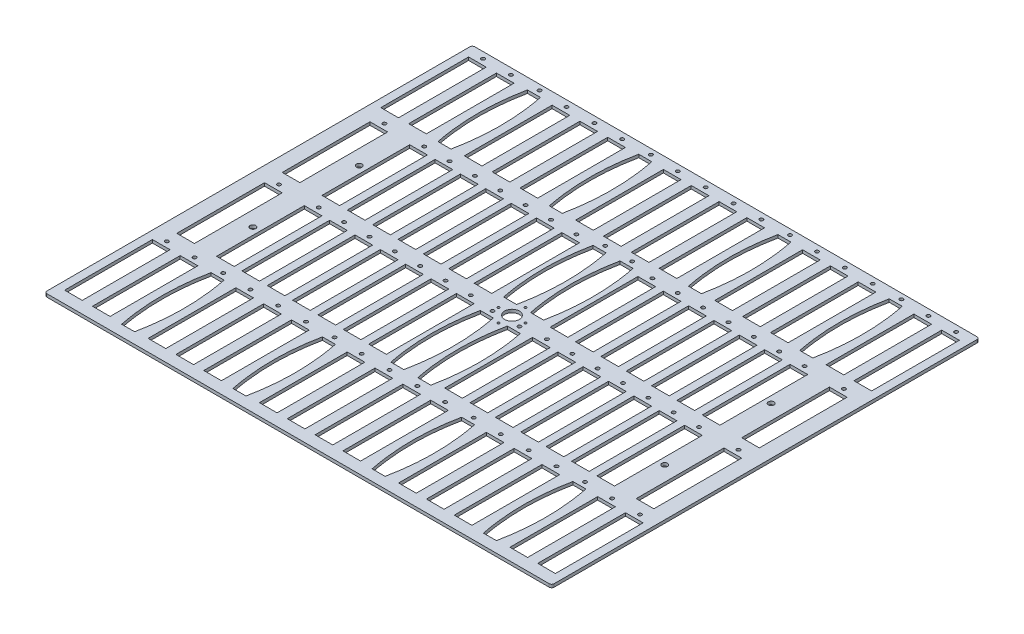
SolidWorks part; units mm, degrees
ref_plane "Front Plane" through (0, 0, 0) normal (0, 0, 1) x (1, 0, 0)
ref_plane "Top Plane" through (0, 0, 0) normal (0, 1, 0) x (1, 0, 0)
ref_plane "Right Plane" through (0, 0, 0) normal (1, 0, 0) x (0, 0, -1)
sketch "Sketch1" plane through (0, 0, 0) normal (0, 1, 0) x (1, 0, 0)
  line L1 (-262.7312, -221.6379) -> (262.7312, -221.6379)
  line L2 (-262.7312, -221.6379) -> (-262.7312, 221.6379)
  line L3 (-262.7312, 221.6379) -> (262.7312, 221.6379)
  line L4 (262.7312, -221.6379) -> (262.7312, 221.6379)
  line L5 (-262.7312, -221.6379) -> (262.7312, 221.6379) construction
  line L6 (-262.7312, 221.6379) -> (262.7312, -221.6379) construction
  point P0 (0, 0)
  dimension "D1" = 525.4625
  dimension "D2" = 443.2757
extrude "Boss-Extrude1" add sketch "Sketch1" along normal blind 3.175
sketch "Sketch2" plane through (0, 3.175, 0) normal (0, 1, 0) x (1, 0, 0)
  circle A0 centre (0, 0) radius 7.62
  dimension "D1" = 15.24
extrude "Cut-Extrude1" cut sketch "Sketch2" against normal through all
hole_wizard "#2 Clearance Hole1" positions "Sketch3" profile "Sketch4" hole size "#2" standard "ANSI Inch" end condition through all
sketch "Sketch3" plane through (0, 3.175, 0) normal (0, 1, 0) x (1, 0, 0)
  line L0 (0, 0) -> (0, 13.97) construction
  line L2 (0, 0) -> (13.97, 0) construction
  line L3 (0, 0) -> (0, -13.97) construction
  line L4 (0, 0) -> (-13.97, 0) construction
  point P194 (0, 13.97)
  point P202 (13.97, 0)
  point P203 (0, -13.97)
  point P204 (-13.97, 0)
  point P205 (0, 0)
  dimension "D1" = 4
  dimension "D2" = 13.97
sketch "Sketch4" plane through (0, 3.175, 0) normal (1, 0, 0) x (0, 0, 1)
  line L0 (0, 0) -> (0, 3.175)
  line L1 (0, 3.175) -> (1.2192, 3.175)
  line L2 (1.2192, 3.175) -> (1.2192, 0)
  line L5 (1.2192, 0) -> (0, 0)
  line L11 (0, -6.35) -> (0, 107.95) construction
  dimension "Thru Hole Dia." = 2.4384
  dimension "Thru Hole Depth" = 3.175
hole_wizard "#1 (0.228) Diameter Hole1" positions "Sketch6" profile "Sketch7" hole size "#1" standard "ANSI Inch" end condition through all
sketch "Sketch6" plane through (0, 3.175, 0) normal (0, 1, 0) x (1, 0, 0)
  line L1 (-213.36, -55.1011) -> (213.36, -55.1011) construction
  line L2 (-213.36, -55.1011) -> (-213.36, 55.1011) construction
  line L3 (-213.36, 55.1011) -> (213.36, 55.1011) construction
  line L4 (213.36, -55.1011) -> (213.36, 55.1011) construction
  line L5 (-213.36, -55.1011) -> (213.36, 55.1011) construction
  line L6 (-213.36, 55.1011) -> (213.36, -55.1011) construction
  circle A0 centre (0, 0) radius 7.62 construction
  point P2 (213.36, 55.1011)
  point P11 (-213.36, -55.1011)
  point P12 (-213.36, 55.1011)
  point P13 (213.36, -55.1011)
  point P26 (-213.36, 55.1011)
  point P28 (213.36, 55.1011)
  point P30 (213.36, -55.1011)
  point P32 (-213.36, -55.1011)
  dimension "D1" = 426.72
  dimension "D2" = 110.2021
  dimension "D3" = 213.36
  dimension "D4" = 55.1011
sketch "Sketch7" plane through (213.36, 3.175, -55.1011) normal (1, 0, 0) x (0, 0, 1)
  line L0 (0, 0) -> (0, 3.175)
  line L1 (0, 3.175) -> (2.8956, 3.175)
  line L2 (2.8956, 3.175) -> (2.8956, 0)
  line L5 (2.8956, 0) -> (0, 0)
  line L11 (0, -6.35) -> (0, 107.95) construction
  dimension "Thru Hole Dia." = 5.7912
  dimension "Thru Hole Depth" = 3.175
sketch "Sketch5" plane through (0, 3.175, 0) normal (0, 1, 0) x (1, 0, 0)
  line L0 (-262.7312, 163.8275) -> (262.7312, 163.8275) construction
  line L1 (-198.8875, 163.8275) -> (-176.0275, 163.8275) construction
  line L2 (-245.1367, 221.6379) -> (-245.1367, -221.6379) construction
  line L3 (-262.7312, 221.6379) -> (-262.7312, -221.6379) construction
  line L4 (-262.7312, -221.6379) -> (262.7312, -221.6379) construction
  line L5 (-216.2971, 221.6379) -> (-216.2971, -221.6379) construction
  line L6 (262.7312, -221.6379) -> (262.7312, 221.6379) construction
  line L7 (-187.4575, 221.6379) -> (-187.4575, -221.6379) construction
  line L8 (-262.7312, 54.6066) -> (262.7312, 54.6066) construction
  line L9 (-262.7312, -54.6142) -> (262.7312, -54.6142) construction
  line L10 (-262.7312, -163.8351) -> (262.7312, -163.8351) construction
  line L11 (262.7312, 221.6379) -> (-262.7312, 221.6379) construction
  line L12 (-158.6179, 221.6379) -> (-158.6179, -221.6379) construction
  line L13 (-129.7783, 221.6379) -> (-129.7783, -221.6379) construction
  line L14 (-100.9388, 221.6379) -> (-100.9388, -221.6379) construction
  line L15 (-72.0992, 221.6379) -> (-72.0992, -221.6379) construction
  line L16 (-43.2596, 221.6379) -> (-43.2596, -221.6379) construction
  line L17 (-14.42, 221.6379) -> (-14.42, -221.6379) construction
  line L18 (14.4196, 221.6379) -> (14.4196, -221.6379) construction
  line L19 (43.2592, 221.6379) -> (43.2592, -221.6379) construction
  line L20 (72.0987, 221.6379) -> (72.0987, -221.6379) construction
  line L21 (100.9383, 221.6379) -> (100.9383, -221.6379) construction
  line L22 (129.7779, 221.6379) -> (129.7779, -221.6379) construction
  line L23 (158.6175, 221.6379) -> (158.6175, -221.6379) construction
  line L24 (187.4571, 221.6379) -> (187.4571, -221.6379) construction
  line L25 (216.2967, 221.6379) -> (216.2967, -221.6379) construction
  line L26 (245.1362, 221.6379) -> (245.1362, -221.6379) construction
  line L27 (-225.4415, 209.2935) -> (-207.1535, 209.2935)
  line L28 (-254.2807, 209.2935) -> (-235.9927, 209.2935)
  line L29 (-254.2807, 209.2935) -> (-254.2807, 118.3615)
  line L30 (-254.2807, 118.3615) -> (-235.9927, 118.3615)
  line L31 (-235.9927, 209.2935) -> (-235.9927, 118.3615)
  line L32 (-254.2807, 209.2935) -> (-235.9927, 118.3615) construction
  line L33 (-254.2807, 118.3615) -> (-235.9927, 209.2935) construction
  line L34 (-254.2807, -118.3691) -> (-235.9927, -118.3691)
  line L35 (-254.2807, -118.3691) -> (-254.2807, -209.3011)
  line L36 (-254.2807, -209.3011) -> (-235.9927, -209.3011)
  line L37 (-235.9927, -118.3691) -> (-235.9927, -209.3011)
  line L38 (-254.2807, -118.3691) -> (-235.9927, -209.3011) construction
  line L39 (-254.2807, -209.3011) -> (-235.9927, -118.3691) construction
  line L40 (-225.4415, 209.2935) -> (-225.4415, 118.3615)
  line L41 (-207.1535, 209.2935) -> (-207.1535, 118.3615)
  line L42 (-225.4415, 118.3615) -> (-207.1535, 118.3615)
  line L43 (-225.4415, -118.3691) -> (-207.1535, -118.3691)
  line L44 (-207.1535, -118.3691) -> (-207.1535, -209.3011)
  line L45 (-225.4415, -118.3691) -> (-225.4415, -209.3011)
  line L46 (-225.4415, -209.3011) -> (-207.1535, -209.3011)
  line L47 (-194.1885, 210.1825) -> (-180.7265, 210.1825)
  line L48 (-194.1885, 210.1825) -> (-194.1885, 117.4725) construction
  line L49 (-194.1885, 117.4725) -> (-180.7265, 117.4725)
  line L50 (-180.7265, 210.1825) -> (-180.7265, 117.4725) construction
  line L51 (-194.1885, 210.1825) -> (-180.7265, 117.4725) construction
  line L52 (-194.1885, 117.4725) -> (-180.7265, 210.1825) construction
  line L53 (-78.8302, 210.1825) -> (-65.3682, 210.1825)
  line L54 (-78.8302, 117.4725) -> (-65.3682, 117.4725)
  line L55 (-167.7632, 209.2935) -> (-149.4752, 209.2935)
  line L56 (-167.7632, 209.2935) -> (-167.7632, 118.3615)
  line L57 (-149.4752, 209.2935) -> (-149.4752, 118.3615)
  line L58 (-167.7632, 118.3615) -> (-149.4752, 118.3615)
  line L59 (-167.7632, -118.3691) -> (-149.4752, -118.3691)
  line L60 (-149.4752, -118.3691) -> (-149.4752, -209.3011)
  line L61 (-167.7632, -118.3691) -> (-167.7632, -209.3011)
  line L62 (-167.7632, -209.3011) -> (-149.4752, -209.3011)
  line L63 (-138.924, 209.2935) -> (-120.636, 209.2935)
  line L64 (-138.924, 209.2935) -> (-138.924, 118.3615)
  line L65 (-120.636, 209.2935) -> (-120.636, 118.3615)
  line L66 (-138.924, 118.3615) -> (-120.636, 118.3615)
  line L67 (-138.924, -118.3691) -> (-120.636, -118.3691)
  line L68 (-120.636, -118.3691) -> (-120.636, -209.3011)
  line L69 (-138.924, -118.3691) -> (-138.924, -209.3011)
  line L70 (-138.924, -209.3011) -> (-120.636, -209.3011)
  line L71 (-110.0849, 209.2935) -> (-91.7969, 209.2935)
  line L72 (-110.0849, 209.2935) -> (-110.0849, 118.3615)
  line L73 (-91.7969, 209.2935) -> (-91.7969, 118.3615)
  line L74 (-110.0849, 118.3615) -> (-91.7969, 118.3615)
  line L75 (-110.0849, -118.3691) -> (-91.7969, -118.3691)
  line L76 (-91.7969, -118.3691) -> (-91.7969, -209.3011)
  line L77 (-110.0849, -118.3691) -> (-110.0849, -209.3011)
  line L78 (-110.0849, -209.3011) -> (-91.7969, -209.3011)
  line L79 (65.3677, 210.1825) -> (78.8297, 210.1825)
  line L80 (65.3677, 117.4725) -> (78.8297, 117.4725)
  line L81 (180.7261, 210.1825) -> (194.1881, 210.1825)
  line L82 (180.7261, 117.4725) -> (194.1881, 117.4725)
  line L83 (-194.1885, -117.6299) -> (-180.7265, -117.6299)
  line L84 (-194.1885, -210.3399) -> (-180.7265, -210.3399)
  line L85 (-78.8302, -117.6299) -> (-65.3682, -117.6299)
  line L86 (-78.8302, -210.3399) -> (-65.3682, -210.3399)
  line L87 (-52.4065, 209.2935) -> (-34.1185, 209.2935)
  line L88 (-52.4065, 209.2935) -> (-52.4065, 118.3615)
  line L89 (-34.1185, 209.2935) -> (-34.1185, 118.3615)
  line L90 (-52.4065, 118.3615) -> (-34.1185, 118.3615)
  line L91 (-52.4065, -118.3691) -> (-34.1185, -118.3691)
  line L92 (-34.1185, -118.3691) -> (-34.1185, -209.3011)
  line L93 (-52.4065, -118.3691) -> (-52.4065, -209.3011)
  line L94 (-52.4065, -209.3011) -> (-34.1185, -209.3011)
  line L95 (-23.5674, 209.2935) -> (-5.2794, 209.2935)
  line L96 (-23.5674, 209.2935) -> (-23.5674, 118.3615)
  line L97 (-5.2794, 209.2935) -> (-5.2794, 118.3615)
  line L98 (-23.5674, 118.3615) -> (-5.2794, 118.3615)
  line L99 (-23.5674, -118.3691) -> (-5.2794, -118.3691)
  line L100 (-5.2794, -118.3691) -> (-5.2794, -209.3011)
  line L101 (-23.5674, -118.3691) -> (-23.5674, -209.3011)
  line L102 (-23.5674, -209.3011) -> (-5.2794, -209.3011)
  line L103 (5.2718, 209.2935) -> (23.5598, 209.2935)
  line L104 (5.2718, 209.2935) -> (5.2718, 118.3615)
  line L105 (23.5598, 209.2935) -> (23.5598, 118.3615)
  line L106 (5.2718, 118.3615) -> (23.5598, 118.3615)
  line L107 (5.2718, -118.3691) -> (23.5598, -118.3691)
  line L108 (23.5598, -118.3691) -> (23.5598, -209.3011)
  line L109 (5.2718, -118.3691) -> (5.2718, -209.3011)
  line L110 (5.2718, -209.3011) -> (23.5598, -209.3011)
  line L111 (34.1109, 209.2935) -> (52.3989, 209.2935)
  line L112 (34.1109, 209.2935) -> (34.1109, 118.3615)
  line L113 (52.3989, 209.2935) -> (52.3989, 118.3615)
  line L114 (34.1109, 118.3615) -> (52.3989, 118.3615)
  line L115 (34.1109, -118.3691) -> (52.3989, -118.3691)
  line L116 (52.3989, -118.3691) -> (52.3989, -209.3011)
  line L117 (34.1109, -118.3691) -> (34.1109, -209.3011)
  line L118 (34.1109, -209.3011) -> (52.3989, -209.3011)
  line L119 (180.7261, -117.6299) -> (194.1881, -117.6299)
  line L120 (180.7261, -210.3399) -> (194.1881, -210.3399)
  line L121 (65.3677, -210.3399) -> (78.8297, -210.3399)
  line L122 (65.3677, -117.6299) -> (78.8297, -117.6299)
  line L127 (91.7892, 209.2935) -> (110.0772, 209.2935)
  line L128 (91.7892, 209.2935) -> (91.7893, 118.3615)
  line L129 (110.0772, 209.2935) -> (110.0773, 118.3615)
  line L130 (91.7893, 118.3615) -> (110.0773, 118.3615)
  line L131 (91.7893, -118.3691) -> (110.0773, -118.3691)
  line L132 (110.0773, -118.3691) -> (110.0773, -209.3011)
  line L133 (91.7893, -118.3691) -> (91.7893, -209.3011)
  line L134 (91.7893, -209.3011) -> (110.0773, -209.3011)
  line L135 (120.6284, 209.2935) -> (138.9164, 209.2935)
  line L136 (120.6284, 209.2935) -> (120.6284, 118.3615)
  line L137 (138.9164, 209.2935) -> (138.9164, 118.3615)
  line L138 (120.6284, 118.3615) -> (138.9164, 118.3615)
  line L139 (120.6284, -118.3691) -> (138.9164, -118.3691)
  line L140 (138.9164, -118.3691) -> (138.9164, -209.3011)
  line L141 (120.6284, -118.3691) -> (120.6284, -209.3011)
  line L142 (120.6284, -209.3011) -> (138.9164, -209.3011)
  line L143 (149.4676, 209.2935) -> (167.7556, 209.2935)
  line L144 (149.4676, 209.2935) -> (149.4676, 118.3615)
  line L145 (167.7556, 209.2935) -> (167.7556, 118.3615)
  line L146 (149.4676, 118.3615) -> (167.7556, 118.3615)
  line L147 (149.4676, -118.3691) -> (167.7556, -118.3691)
  line L148 (167.7556, -118.3691) -> (167.7556, -209.3011)
  line L149 (149.4676, -118.3691) -> (149.4676, -209.3011)
  line L150 (149.4676, -209.3011) -> (167.7556, -209.3011)
  line L159 (207.1459, 209.2935) -> (225.4339, 209.2935)
  line L160 (207.1459, 209.2935) -> (207.1459, 118.3615)
  line L161 (225.4339, 209.2935) -> (225.4339, 118.3615)
  line L162 (207.1459, 118.3615) -> (225.4339, 118.3615)
  line L163 (207.1459, -118.3691) -> (225.4339, -118.3691)
  line L164 (225.4339, -118.3691) -> (225.4339, -209.3011)
  line L165 (207.1459, -118.3691) -> (207.1459, -209.3011)
  line L166 (207.1459, -209.3011) -> (225.4339, -209.3011)
  line L167 (235.985, 209.2935) -> (254.2731, 209.2935)
  line L168 (235.985, 209.2935) -> (235.9851, 118.3615)
  line L169 (254.2731, 209.2935) -> (254.2731, 118.3615)
  line L170 (235.9851, 118.3615) -> (254.2731, 118.3615)
  line L171 (235.9851, -118.3691) -> (254.2731, -118.3691)
  line L172 (254.2731, -118.3691) -> (254.2731, -209.3011)
  line L173 (235.9851, -118.3691) -> (235.9851, -209.3011)
  line L174 (235.9851, -209.3011) -> (254.2731, -209.3011)
  line L337 (-178.3143, 209.2935) -> (-178.3143, 118.3615) [skipped]
  line L338 (-196.6023, 118.3615) -> (-178.3143, 118.3615) [skipped]
  line L339 (-196.6023, 209.2935) -> (-196.6023, 118.3615) [skipped]
  line L340 (-196.6023, 209.2935) -> (-178.3143, 209.2935) [skipped]
  line L341 (-62.9577, 209.2935) -> (-62.9577, 118.3615) [skipped]
  line L342 (-81.2457, 209.2935) -> (-62.9577, 209.2935) [skipped]
  line L343 (-81.2457, 209.2935) -> (-81.2457, 118.3615) [skipped]
  line L344 (-81.2457, 118.3615) -> (-62.9577, 118.3615) [skipped]
  line L345 (-196.6023, -118.3691) -> (-178.3143, -118.3691) [skipped]
  line L346 (-196.6023, -209.3011) -> (-178.3143, -209.3011) [skipped]
  line L347 (-178.3143, -118.3691) -> (-178.3143, -209.3011) [skipped]
  line L348 (-196.6023, -118.3691) -> (-196.6023, -209.3011) [skipped]
  line L349 (-81.2457, -118.3691) -> (-62.9577, -118.3691) [skipped]
  line L350 (-81.2457, -118.3691) -> (-81.2457, -209.3011) [skipped]
  line L351 (-62.9577, -118.3691) -> (-62.9577, -209.3011) [skipped]
  line L352 (-81.2457, -209.3011) -> (-62.9577, -209.3011) [skipped]
  line L353 (178.3067, -118.3691) -> (196.5947, -118.3691) [skipped]
  line L354 (196.5947, -118.3691) -> (196.5947, -209.3011) [skipped]
  line L355 (178.3067, -118.3691) -> (178.3067, -209.3011) [skipped]
  line L356 (178.3067, -209.3011) -> (196.5947, -209.3011) [skipped]
  line L357 (62.9501, -209.3011) -> (81.2381, -209.3011) [skipped]
  line L358 (81.2381, -118.3691) -> (81.2381, -209.3011) [skipped]
  line L359 (62.9501, -118.3691) -> (62.9501, -209.3011) [skipped]
  line L360 (62.9501, -118.3691) -> (81.2381, -118.3691) [skipped]
  line L361 (178.3067, 118.3615) -> (196.5947, 118.3615) [skipped]
  line L362 (196.5947, 209.2935) -> (196.5947, 118.3615) [skipped]
  line L363 (178.3067, 209.2935) -> (178.3067, 118.3615) [skipped]
  line L364 (178.3067, 209.2935) -> (196.5947, 209.2935) [skipped]
  line L365 (62.9501, 118.3615) -> (81.2381, 118.3615) [skipped]
  line L366 (62.9501, 209.2935) -> (62.9501, 118.3615) [skipped]
  line L367 (81.2381, 209.2935) -> (81.2381, 118.3615) [skipped]
  line L368 (62.9501, 209.2935) -> (81.2381, 209.2935) [skipped]
  circle A0 centre (-245.1367, 215.1355) radius 1.8288
  circle A1 centre (-245.1367, -112.5271) radius 1.8288
  circle A2 centre (-216.2975, 215.1355) radius 1.8288
  circle A3 centre (-216.2975, -112.5271) radius 1.8288
  circle A4 centre (-187.4575, 216.0245) radius 1.8288
  circle A5 centre (-72.0992, 216.0245) radius 1.8288
  circle A6 centre (-158.6192, 215.1355) radius 1.8288
  circle A7 centre (-158.6192, -112.5271) radius 1.8288
  circle A8 centre (-129.78, 215.1355) radius 1.8288
  circle A9 centre (-129.78, -112.5271) radius 1.8288
  circle A10 centre (-100.9409, 215.1355) radius 1.8288
  circle A11 centre (-100.9409, -112.5271) radius 1.8288
  circle A12 centre (72.0987, 216.0245) radius 1.8288
  circle A13 centre (187.4571, 216.0245) radius 1.8288
  circle A14 centre (-43.2625, 215.1355) radius 1.8288
  circle A15 centre (-43.2625, -112.5271) radius 1.8288
  circle A16 centre (-14.4234, 215.1355) radius 1.8288
  circle A17 centre (-14.4234, -112.5271) radius 1.8288
  circle A18 centre (14.4158, 215.1355) radius 1.8288
  circle A19 centre (14.4158, -112.5271) radius 1.8288
  circle A20 centre (43.2549, 215.1355) radius 1.8288
  circle A21 centre (43.2549, -112.5271) radius 1.8288
  circle A22 centre (-187.4575, -111.7879) radius 1.8288
  circle A23 centre (-72.0992, -111.7879) radius 1.8288
  circle A24 centre (100.9333, 215.1355) radius 1.8288
  circle A25 centre (100.9333, -112.5271) radius 1.8288
  circle A26 centre (129.7724, 215.1355) radius 1.8288
  circle A27 centre (129.7724, -112.5271) radius 1.8288
  circle A28 centre (158.6116, 215.1355) radius 1.8288
  circle A29 centre (158.6116, -112.5271) radius 1.8288
  circle A30 centre (187.4571, -111.7879) radius 1.8288
  circle A31 centre (72.0987, -111.7879) radius 1.8288
  circle A32 centre (216.2899, 215.1355) radius 1.8288
  circle A33 centre (216.2899, -112.5271) radius 1.8288
  circle A34 centre (245.129, 215.1355) radius 1.8288
  circle A35 centre (245.1291, -112.5271) radius 1.8288
  circle A36 centre (-72.1017, 215.1355) radius 1.8288 [skipped]
  circle A37 centre (-187.4583, 215.1355) radius 1.8288 [skipped]
  circle A38 centre (-187.4583, -112.5271) radius 1.8288 [skipped]
  circle A39 centre (-72.1017, -112.5271) radius 1.8288 [skipped]
  circle A40 centre (187.4507, -112.5271) radius 1.8288 [skipped]
  circle A41 centre (72.0941, -112.5271) radius 1.8288 [skipped]
  circle A42 centre (187.4507, 215.1355) radius 1.8288 [skipped]
  circle A43 centre (72.0941, 215.1355) radius 1.8288 [skipped]
  spline S0 degree 2 poles (-180.7265, 210.1825) (-171.3285, 163.8275) (-180.7265, 117.4725) knots 0 0 0 1 1 1
  spline S1 degree 2 poles (-194.1885, 210.1825) (-203.5865, 163.8275) (-194.1885, 117.4725) knots 0 0 0 1 1 1
  spline S2 degree 2 poles (-78.8302, 210.1825) (-88.2282, 163.8275) (-78.8302, 117.4725) knots 0 0 0 1 1 1
  spline S3 degree 2 poles (-65.3682, 210.1825) (-55.9702, 163.8275) (-65.3682, 117.4725) knots 0 0 0 1 1 1
  spline S4 degree 2 poles (65.3677, 210.1825) (55.9697, 163.8275) (65.3677, 117.4725) knots 0 0 0 1 1 1
  spline S5 degree 2 poles (78.8297, 210.1825) (88.2277, 163.8275) (78.8297, 117.4725) knots 0 0 0 1 1 1
  spline S6 degree 2 poles (194.1881, 210.1825) (203.5861, 163.8275) (194.1881, 117.4725) knots 0 0 0 1 1 1
  spline S7 degree 2 poles (180.7261, 210.1825) (171.3281, 163.8275) (180.7261, 117.4725) knots 0 0 0 1 1 1
  spline S8 degree 2 poles (-194.1885, -117.6299) (-203.5865, -163.9849) (-194.1885, -210.3399) knots 0 0 0 1 1 1
  spline S9 degree 2 poles (-180.7265, -117.6299) (-171.3285, -163.9849) (-180.7265, -210.3399) knots 0 0 0 1 1 1
  spline S10 degree 2 poles (-65.3682, -117.6299) (-55.9702, -163.9849) (-65.3682, -210.3399) knots 0 0 0 1 1 1
  spline S11 degree 2 poles (-78.8302, -117.6299) (-88.2282, -163.9849) (-78.8302, -210.3399) knots 0 0 0 1 1 1
  spline S12 degree 2 poles (194.1881, -117.6299) (203.5861, -163.9849) (194.1881, -210.3399) knots 0 0 0 1 1 1
  spline S13 degree 2 poles (180.7261, -117.6299) (171.3281, -163.9849) (180.7261, -210.3399) knots 0 0 0 1 1 1
  spline S14 degree 2 poles (78.8297, -117.6299) (88.2277, -163.9849) (78.8297, -210.3399) knots 0 0 0 1 1 1
  spline S15 degree 2 poles (65.3677, -117.6299) (55.9697, -163.9849) (65.3677, -210.3399) knots 0 0 0 1 1 1
  point P18 (-245.1367, 163.8275)
  point P57 (-245.1367, -163.8351)
  point P66 (-187.4575, 163.8275)
  point P86 (-187.4575, 163.8275)
  dimension "D6" = 3.6576
  dimension "D7" = 5.842
  dimension "D8" = 5.842
  dimension "D13" = 5.842
  dimension "D1" = 4
  dimension "D3" = 17.5946
  dimension "D5" = 90.932
  dimension "D2" = 57.8104
  dimension "D4" = 18.288
  dimension "D10" = 13.462
  dimension "D11" = 92.71
  dimension "D12" = 22.86
  dimension "D9" = 18
  dimension "D14" = 2
  dimension "D15" = 2
extrude "Cut-Extrude3" cut sketch "Sketch5" against normal blind 3.175
hole_wizard "#6 Clearance Hole2" positions "Sketch9" profile "Sketch10" hole size "#6" standard "ANSI Inch" end condition through all
sketch "Sketch9" plane through (0, 3.175, 0) normal (0, 1, 0) x (1, 0, 0)
  line L0 (-245.1367, 209.2935) -> (-245.1367, 215.1355) construction
  line L1 (-235.9927, 209.2935) -> (-254.2807, 209.2935) construction
  point P2 (-245.1367, 215.1355)
  dimension "D1" = 5.842
sketch "Sketch10" plane through (-245.1367, 3.175, -215.1355) normal (1, 0, 0) x (0, 0, 1)
  line L0 (0, 0) -> (0, 3.175)
  line L1 (0, 3.175) -> (1.8288, 3.175)
  line L2 (1.8288, 3.175) -> (1.8288, 0)
  line L5 (1.8288, 0) -> (0, 0)
  line L11 (0, -6.35) -> (0, 107.95) construction
  dimension "Thru Hole Dia." = 3.6576
  dimension "Thru Hole Depth" = 3.175
sketch "Sketch11" plane through (0, 3.175, 0) normal (0, 1, 0) x (1, 0, 0)
  line L0 (-262.7312, 163.8275) -> (262.7312, 163.8275) construction
  line L1 (-262.7312, 221.6379) -> (-262.7312, -221.6379) construction
  line L2 (262.7312, -221.6379) -> (262.7312, 221.6379) construction
  line L3 (262.7312, 221.6379) -> (-262.7312, 221.6379) construction
  line L4 (-262.7312, 54.5567) -> (262.7312, 54.5567) construction
  line L5 (-262.7312, -54.7141) -> (262.7312, -54.7141) construction
  line L6 (-262.7312, -163.9849) -> (262.7312, -163.9849) construction
  line L7 (-238.045, 100.0227) -> (-238.045, 105.8647) construction
  line L8 (-247.189, 100.0227) -> (-228.901, 100.0227)
  line L9 (-247.189, 100.0227) -> (-247.189, 9.0907)
  line L10 (-247.189, 9.0907) -> (-228.901, 9.0907)
  line L11 (-228.901, 100.0227) -> (-228.901, 9.0907)
  line L12 (-247.189, 100.0227) -> (-228.901, 9.0907) construction
  line L13 (-247.189, 9.0907) -> (-228.901, 100.0227) construction
  line L14 (228.901, 100.0227) -> (247.189, 100.0227)
  line L15 (228.901, 100.0227) -> (228.901, 9.0907)
  line L16 (247.189, 100.0227) -> (247.189, 9.0907)
  line L17 (228.901, 9.0907) -> (247.189, 9.0907)
  line L18 (228.901, -9.2481) -> (247.189, -9.2481)
  line L19 (228.901, -9.2481) -> (228.901, -100.1801)
  line L20 (247.189, -9.2481) -> (247.189, -100.1801)
  line L21 (228.901, -100.1801) -> (247.189, -100.1801)
  line L22 (-247.189, -9.2481) -> (-228.901, -9.2481)
  line L23 (-247.189, -9.2481) -> (-247.189, -100.1801)
  line L24 (-228.901, -9.2481) -> (-228.901, -100.1801)
  line L25 (-247.189, -100.1801) -> (-228.901, -100.1801)
  circle A0 centre (-238.045, 105.8647) radius 1.8288
  circle A1 centre (238.045, 105.8647) radius 1.8288
  circle A2 centre (238.045, -3.4061) radius 1.8288
  circle A3 centre (-238.045, -3.4061) radius 1.8288
  point P8 (-238.045, 54.5567)
  dimension "D5" = 3.6576
  dimension "D1" = 57.8104
  dimension "D2" = 24.6863
  dimension "D3" = 18.288
  dimension "D4" = 90.932
  dimension "D6" = 5.842
extrude "Cut-Extrude5" cut sketch "Sketch11" against normal blind 3.175
sketch "Sketch12" plane through (0, 3.175, 0) normal (0, 1, 0) x (1, 0, 0)
  line L0 (-228.901, 54.5567) -> (228.901, 54.5567) construction
  line L1 (-228.901, 9.0907) -> (-228.901, 100.0227) construction
  line L2 (228.901, 100.0227) -> (228.901, 9.0907) construction
  line L3 (-213.36, 55.1011) -> (-213.36, 247.1712) construction
  line L4 (-247.189, 9.0907) -> (-228.901, 9.0907) construction
  line L5 (-205.994, 100.0227) -> (-187.706, 100.0227)
  line L6 (-205.994, 100.0227) -> (-205.994, 9.0907)
  line L7 (-205.994, 9.0907) -> (-187.706, 9.0907)
  line L8 (-187.706, 100.0227) -> (-187.706, 9.0907)
  line L9 (-205.994, 100.0227) -> (-187.706, 9.0907) construction
  line L10 (-205.994, 9.0907) -> (-187.706, 100.0227) construction
  line L11 (-196.85, 100.0227) -> (-196.85, 105.8647) construction
  line L12 (-179.7209, 100.0227) -> (-161.4329, 100.0227)
  line L13 (-179.7209, 100.0227) -> (-179.7209, 9.0907)
  line L14 (-161.4329, 100.0227) -> (-161.4329, 9.0907)
  line L15 (-179.7209, 9.0907) -> (-161.4329, 9.0907)
  line L16 (-153.4477, 100.0227) -> (-135.1597, 100.0227)
  line L17 (-153.4477, 100.0227) -> (-153.4477, 9.0907)
  line L18 (-135.1597, 100.0227) -> (-135.1597, 9.0907)
  line L19 (-153.4477, 9.0907) -> (-135.1597, 9.0907)
  line L20 (-127.1746, 100.0227) -> (-108.8866, 100.0227)
  line L21 (-127.1746, 100.0227) -> (-127.1746, 9.0907)
  line L22 (-108.8866, 100.0227) -> (-108.8866, 9.0907)
  line L23 (-127.1746, 9.0907) -> (-108.8866, 9.0907)
  line L24 (-100.9015, 100.0227) -> (-82.6135, 100.0227)
  line L25 (-100.9015, 100.0227) -> (-100.9015, 9.0907)
  line L26 (-82.6135, 100.0227) -> (-82.6135, 9.0907)
  line L27 (-100.9015, 9.0907) -> (-82.6135, 9.0907)
  line L28 (-74.6284, 100.0227) -> (-56.3404, 100.0227)
  line L29 (-74.6284, 100.0227) -> (-74.6284, 9.0907)
  line L30 (-56.3404, 100.0227) -> (-56.3404, 9.0907)
  line L31 (-74.6284, 9.0907) -> (-56.3404, 9.0907)
  line L32 (-48.3552, 100.0227) -> (-30.0672, 100.0227)
  line L33 (-48.3552, 100.0227) -> (-48.3552, 9.0907)
  line L34 (-30.0672, 100.0227) -> (-30.0672, 9.0907)
  line L35 (-48.3552, 9.0907) -> (-30.0672, 9.0907)
  line L36 (0, 0) -> (0, 123.4666) construction
  line L37 (-13.97, 58.3667) -> (13.97, 58.3667) construction
  line L38 (-2.54, 58.3667) -> (-25.4, 58.3667) construction
  line L39 (-7.239, 104.7217) -> (-20.701, 104.7217)
  line L40 (-7.239, 104.7217) -> (-7.239, 12.0117) construction
  line L41 (-7.239, 12.0117) -> (-20.701, 12.0117)
  line L42 (-20.701, 104.7217) -> (-20.701, 12.0117) construction
  line L43 (-7.239, 104.7217) -> (-20.701, 12.0117) construction
  line L44 (30.4641, 100.0227) -> (48.7521, 100.0227)
  line L45 (30.4641, 100.0227) -> (30.4641, 9.0907)
  line L46 (48.7521, 100.0227) -> (48.7521, 9.0907)
  line L47 (30.4641, 9.0907) -> (48.7521, 9.0907)
  line L48 (56.7373, 100.0227) -> (75.0253, 100.0227)
  line L49 (56.7373, 100.0227) -> (56.7373, 9.0907)
  line L50 (75.0253, 100.0227) -> (75.0253, 9.0907)
  line L51 (56.7373, 9.0907) -> (75.0253, 9.0907)
  line L52 (83.0104, 100.0227) -> (101.2984, 100.0227)
  line L53 (83.0104, 100.0227) -> (83.0104, 9.0907)
  line L54 (101.2984, 100.0227) -> (101.2984, 9.0907)
  line L55 (83.0104, 9.0907) -> (101.2984, 9.0907)
  line L56 (109.2835, 100.0227) -> (127.5715, 100.0227)
  line L57 (109.2835, 100.0227) -> (109.2835, 9.0907)
  line L58 (127.5715, 100.0227) -> (127.5715, 9.0907)
  line L59 (109.2835, 9.0907) -> (127.5715, 9.0907)
  line L60 (135.5566, 100.0227) -> (153.8446, 100.0227)
  line L61 (135.5566, 100.0227) -> (135.5566, 9.0907)
  line L62 (153.8446, 100.0227) -> (153.8446, 9.0907)
  line L63 (135.5566, 9.0907) -> (153.8446, 9.0907)
  line L64 (161.8298, 100.0227) -> (180.1178, 100.0227)
  line L65 (161.8298, 100.0227) -> (161.8298, 9.0907)
  line L66 (180.1178, 100.0227) -> (180.1178, 9.0907)
  line L67 (161.8298, 9.0907) -> (180.1178, 9.0907)
  line L68 (188.1029, 100.0227) -> (206.3909, 100.0227)
  line L69 (188.1029, 100.0227) -> (188.1029, 9.0907)
  line L70 (206.3909, 100.0227) -> (206.3909, 9.0907)
  line L71 (188.1029, 9.0907) -> (206.3909, 9.0907)
  line L72 (-179.7209, -9.2481) -> (-161.4329, -9.2481)
  line L73 (-179.7209, -9.2481) -> (-179.7209, -100.1801)
  line L74 (-161.4329, -9.2481) -> (-161.4329, -100.1801)
  line L75 (-179.7209, -100.1801) -> (-161.4329, -100.1801)
  line L76 (-153.4477, -9.2481) -> (-135.1597, -9.2481)
  line L77 (-153.4477, -9.2481) -> (-153.4477, -100.1801)
  line L78 (-135.1597, -9.2481) -> (-135.1597, -100.1801)
  line L79 (-153.4477, -100.1801) -> (-135.1597, -100.1801)
  line L80 (-127.1746, -9.2481) -> (-108.8866, -9.2481)
  line L81 (-127.1746, -9.2481) -> (-127.1746, -100.1801)
  line L82 (-108.8866, -9.2481) -> (-108.8866, -100.1801)
  line L83 (-127.1746, -100.1801) -> (-108.8866, -100.1801)
  line L84 (-100.9015, -9.2481) -> (-82.6135, -9.2481)
  line L85 (-100.9015, -9.2481) -> (-100.9015, -100.1801)
  line L86 (-82.6135, -9.2481) -> (-82.6135, -100.1801)
  line L87 (-100.9015, -100.1801) -> (-82.6135, -100.1801)
  line L88 (-74.6284, -9.2481) -> (-56.3404, -9.2481)
  line L89 (-74.6284, -9.2481) -> (-74.6284, -100.1801)
  line L90 (-56.3404, -9.2481) -> (-56.3404, -100.1801)
  line L91 (-74.6284, -100.1801) -> (-56.3404, -100.1801)
  line L92 (-48.3552, -9.2481) -> (-30.0672, -9.2481)
  line L93 (-48.3552, -9.2481) -> (-48.3552, -100.1801)
  line L94 (-30.0672, -9.2481) -> (-30.0672, -100.1801)
  line L95 (-48.3552, -100.1801) -> (-30.0672, -100.1801)
  line L96 (-7.239, 12.0117) -> (-20.701, 104.7217) construction
  line L97 (-13.97, 104.7217) -> (-13.97, 110.5637) construction
  line L98 (2.54, 58.3667) -> (25.4, 58.3667) construction
  line L99 (7.239, 12.0117) -> (20.701, 12.0117)
  line L100 (7.239, 12.0117) -> (7.239, 104.7217) construction
  line L101 (7.239, 104.7217) -> (20.701, 104.7217)
  line L102 (20.701, 12.0117) -> (20.701, 104.7217) construction
  line L103 (7.239, 12.0117) -> (20.701, 104.7217) construction
  line L104 (30.4641, -9.2481) -> (48.7521, -9.2481)
  line L105 (30.4641, -9.2481) -> (30.4641, -100.1801)
  line L106 (48.7521, -9.2481) -> (48.7521, -100.1801)
  line L107 (30.4641, -100.1801) -> (48.7521, -100.1801)
  line L108 (56.7373, -9.2481) -> (75.0253, -9.2481)
  line L109 (56.7373, -9.2481) -> (56.7373, -100.1801)
  line L110 (75.0253, -9.2481) -> (75.0253, -100.1801)
  line L111 (56.7373, -100.1801) -> (75.0253, -100.1801)
  line L112 (83.0104, -9.2481) -> (101.2984, -9.2481)
  line L113 (83.0104, -9.2481) -> (83.0104, -100.1801)
  line L114 (101.2984, -9.2481) -> (101.2984, -100.1801)
  line L115 (83.0104, -100.1801) -> (101.2984, -100.1801)
  line L116 (109.2835, -9.2481) -> (127.5715, -9.2481)
  line L117 (109.2835, -9.2481) -> (109.2835, -100.1801)
  line L118 (127.5715, -9.2481) -> (127.5715, -100.1801)
  line L119 (109.2835, -100.1801) -> (127.5715, -100.1801)
  line L120 (135.5566, -9.2481) -> (153.8446, -9.2481)
  line L121 (135.5566, -9.2481) -> (135.5566, -100.1801)
  line L122 (153.8446, -9.2481) -> (153.8446, -100.1801)
  line L123 (135.5566, -100.1801) -> (153.8446, -100.1801)
  line L124 (161.8298, -9.2481) -> (180.1178, -9.2481)
  line L125 (161.8298, -9.2481) -> (161.8298, -100.1801)
  line L126 (180.1178, -9.2481) -> (180.1178, -100.1801)
  line L127 (161.8298, -100.1801) -> (180.1178, -100.1801)
  line L128 (188.1029, -9.2481) -> (206.3909, -9.2481)
  line L129 (188.1029, -9.2481) -> (188.1029, -100.1801)
  line L130 (206.3909, -9.2481) -> (206.3909, -100.1801)
  line L131 (188.1029, -100.1801) -> (206.3909, -100.1801)
  line L132 (-205.994, -9.2481) -> (-187.706, -9.2481)
  line L133 (-205.994, -9.2481) -> (-205.994, -100.1801)
  line L134 (-187.706, -9.2481) -> (-187.706, -100.1801)
  line L135 (-205.994, -100.1801) -> (-187.706, -100.1801)
  line L136 (-22.0821, 100.0227) -> (-3.7941, 100.0227) [skipped]
  line L137 (-22.0821, 100.0227) -> (-22.0821, 9.0907) [skipped]
  line L138 (-3.7941, 100.0227) -> (-3.7941, 9.0907) [skipped]
  line L139 (-22.0821, 9.0907) -> (-3.7941, 9.0907) [skipped]
  line L140 (4.191, 100.0227) -> (22.479, 100.0227) [skipped]
  line L141 (4.191, 100.0227) -> (4.191, 9.0907) [skipped]
  line L142 (22.479, 100.0227) -> (22.479, 9.0907) [skipped]
  line L143 (4.191, 9.0907) -> (22.479, 9.0907) [skipped]
  line L144 (-22.0821, -9.2481) -> (-3.7941, -9.2481) [skipped]
  line L145 (-22.0821, -9.2481) -> (-22.0821, -100.1801) [skipped]
  line L146 (-3.7941, -9.2481) -> (-3.7941, -100.1801) [skipped]
  line L147 (-22.0821, -100.1801) -> (-3.7941, -100.1801) [skipped]
  line L148 (4.191, -9.2481) -> (22.479, -9.2481) [skipped]
  line L149 (4.191, -9.2481) -> (4.191, -100.1801) [skipped]
  line L150 (22.479, -9.2481) -> (22.479, -100.1801) [skipped]
  line L151 (4.191, -100.1801) -> (22.479, -100.1801) [skipped]
  line L152 (7.239, 104.7217) -> (20.701, 12.0117) construction
  line L154 (13.97, 104.7217) -> (13.97, 110.5637) construction
  line L155 (-7.239, -12.1183) -> (-20.701, -12.1183)
  line L156 (7.239, -12.1183) -> (20.701, -12.1183)
  line L157 (7.239, -104.8283) -> (20.701, -104.8283)
  line L158 (-7.239, -104.8283) -> (-20.701, -104.8283)
  circle A0 centre (-196.85, 105.8647) radius 1.8288
  circle A1 centre (-238.045, 105.8647) radius 1.8288 construction
  circle A2 centre (-170.5769, 105.8647) radius 1.8288
  circle A3 centre (-144.3037, 105.8647) radius 1.8288
  circle A4 centre (-118.0306, 105.8647) radius 1.8288
  circle A5 centre (-91.7575, 105.8647) radius 1.8288
  circle A6 centre (-65.4844, 105.8647) radius 1.8288
  circle A7 centre (-39.2112, 105.8647) radius 1.8288
  circle A8 centre (-13.97, 110.5637) radius 1.8288
  circle A9 centre (13.97, 110.5637) radius 1.8288
  circle A10 centre (39.6081, 105.8647) radius 1.8288
  circle A11 centre (65.8813, 105.8647) radius 1.8288
  circle A12 centre (92.1544, 105.8647) radius 1.8288
  circle A13 centre (118.4275, 105.8647) radius 1.8288
  circle A14 centre (144.7006, 105.8647) radius 1.8288
  circle A15 centre (170.9738, 105.8647) radius 1.8288
  circle A16 centre (197.2469, 105.8647) radius 1.8288
  circle A17 centre (-170.5769, -3.4061) radius 1.8288
  circle A18 centre (-144.3037, -3.4061) radius 1.8288
  circle A19 centre (-118.0306, -3.4061) radius 1.8288
  circle A20 centre (-91.7575, -3.4061) radius 1.8288
  circle A21 centre (-65.4844, -3.4061) radius 1.8288
  circle A22 centre (-39.2112, -3.4061) radius 1.8288
  circle A23 centre (13.97, -6.2763) radius 1.8288
  circle A24 centre (-13.97, -6.2763) radius 1.8288
  circle A25 centre (39.6081, -3.4061) radius 1.8288
  circle A26 centre (65.8813, -3.4061) radius 1.8288
  circle A27 centre (92.1544, -3.4061) radius 1.8288
  circle A28 centre (118.4275, -3.4061) radius 1.8288
  circle A29 centre (144.7006, -3.4061) radius 1.8288
  circle A30 centre (170.9738, -3.4061) radius 1.8288
  circle A31 centre (197.2469, -3.4061) radius 1.8288
  circle A32 centre (-196.85, -3.4061) radius 1.8288
  circle A33 centre (-12.9381, 105.8647) radius 1.8288 [skipped]
  circle A34 centre (13.335, 105.8647) radius 1.8288 [skipped]
  circle A35 centre (-12.9381, -3.4061) radius 1.8288 [skipped]
  circle A36 centre (13.335, -3.4061) radius 1.8288 [skipped]
  spline S0 degree 2 poles (-20.701, 104.7217) (-30.099, 58.3667) (-20.701, 12.0117) knots 0 0 0 1 1 1
  spline S1 degree 2 poles (-7.239, 104.7217) (2.159, 58.3667) (-7.239, 12.0117) knots 0 0 0 1 1 1
  spline S2 degree 2 poles (20.701, 104.7217) (30.099, 58.3667) (20.701, 12.0117) knots 0 0 0 1 1 1
  spline S3 degree 2 poles (7.239, 104.7217) (-2.159, 58.3667) (7.239, 12.0117) knots 0 0 0 1 1 1
  spline S4 degree 2 poles (-7.239, -12.1183) (2.159, -58.4733) (-7.239, -104.8283) knots 0 0 0 1 1 1
  spline S5 degree 2 poles (-20.701, -12.1183) (-30.099, -58.4733) (-20.701, -104.8283) knots 0 0 0 1 1 1
  spline S6 degree 2 poles (7.239, -12.1183) (-2.159, -58.4733) (7.239, -104.8283) knots 0 0 0 1 1 1
  spline S7 degree 2 poles (20.701, -12.1183) (30.099, -58.4733) (20.701, -104.8283) knots 0 0 0 1 1 1
  point P9 (-196.85, 54.5567)
  point P61 (0, 58.3667)
  point P69 (-13.97, 58.3667)
  point P159 (13.97, 58.3667)
  dimension "D1" = 5.842
  dimension "D8" = 92.71
  dimension "D2" = 16.51
  dimension "D5" = 3.81
  dimension "D6" = 27.94
  dimension "D7" = 13.462
  dimension "D9" = 22.86
  dimension "D10" = 5.842
  dimension "D11" = 30.0672
  dimension "D3" = 16
  dimension "D4" = 2
  dimension "D13" = 2
  dimension "D14" = 2
extrude "Cut-Extrude6" cut sketch "Sketch12" against normal blind 3.175
fillet "Fillet1" radius 2.54 4 edges at (-262.7312, 1.5875, -221.6379) (-262.7312, 1.5875, 221.6379) (262.7312, 1.5875, 221.6379) (262.7312, 1.5875, -221.6379)
